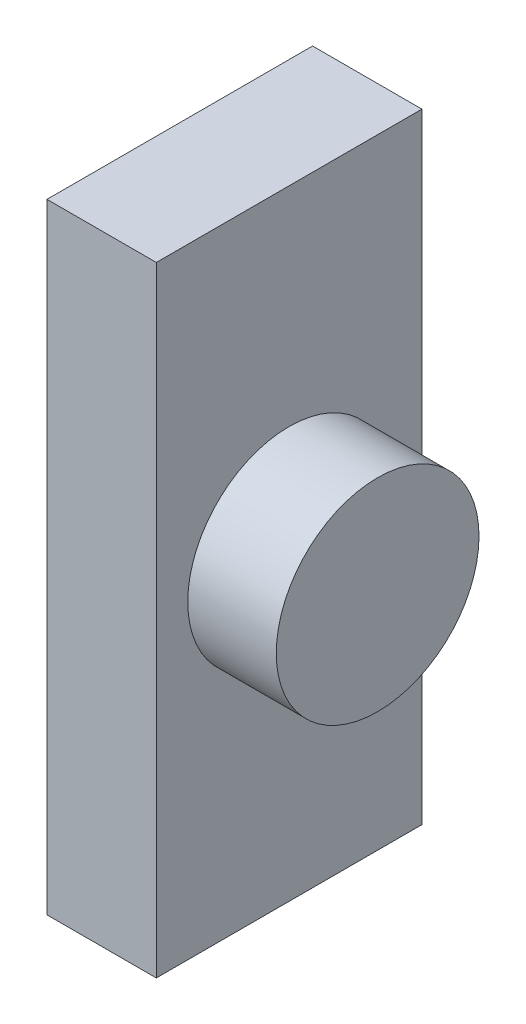
SolidWorks part; units mm, degrees
ref_plane "Front Plane" through (0, 0, 0) normal (0, 0, 1) x (1, 0, 0)
ref_plane "Top Plane" through (0, 0, 0) normal (0, 1, 0) x (1, 0, 0)
ref_plane "Right Plane" through (0, 0, 0) normal (1, 0, 0) x (0, 0, -1)
sketch "Sketch1" plane through (0, 0, 0) normal (1, 0, 0) x (0, 0, -1)
  line L0 (5.9125, 17.5) -> (9.0875, 17.5) construction
  line L1 (5.9125, 24) -> (9.0875, 24)
  line L2 (5.9125, 24) -> (5.9125, 11)
  line L3 (5.9125, 11) -> (9.0875, 11)
  line L4 (9.0875, 24) -> (9.0875, 11)
  line L5 (7.5, 24) -> (7.5, 11) construction
  line L6 (7.5, 35) -> (7.5, 0) construction
  line L15 (0, 35) -> (15, 35)
  line L16 (0, 35) -> (0, 0)
  line L17 (0, 0) -> (15, 0)
  line L18 (15, 35) -> (15, 0)
  line L19 (0, 17.5) -> (15, 17.5) construction
  dimension "D2" = 3.175
  dimension "D3" = 13
  dimension "D4" = 15
  dimension "D5" = 35
extrude "Boss-Extrude1" add sketch "Sketch1" along normal blind 4.175
sketch "Sketch2" plane through (4.175, 0, 0) normal (1, 0, 0) x (0, 0, -1)
  line L1 (0, 35) -> (15, 35)
  line L2 (0, 35) -> (0, 0)
  line L3 (0, 0) -> (15, 0)
  line L4 (15, 35) -> (15, 0)
extrude "Boss-Extrude2" add sketch "Sketch2" along normal blind 2
sketch "Sketch3" plane through (6.175, 0, 0) normal (1, 0, 0) x (0, 0, -1)
  line L0 (7.5, 35) -> (7.5, 0) construction
  line L1 (15, 35) -> (0, 35) construction
  line L2 (0, 0) -> (15, 0) construction
  line L3 (0, 17.5) -> (15, 17.5) construction
  line L4 (0, 35) -> (0, 0) construction
  line L5 (15, 0) -> (15, 35) construction
  circle A0 centre (7.5, 17.5) radius 5.725
  dimension "D1" = 11.45
extrude "Boss-Extrude3" add sketch "Sketch3" along normal blind 5
